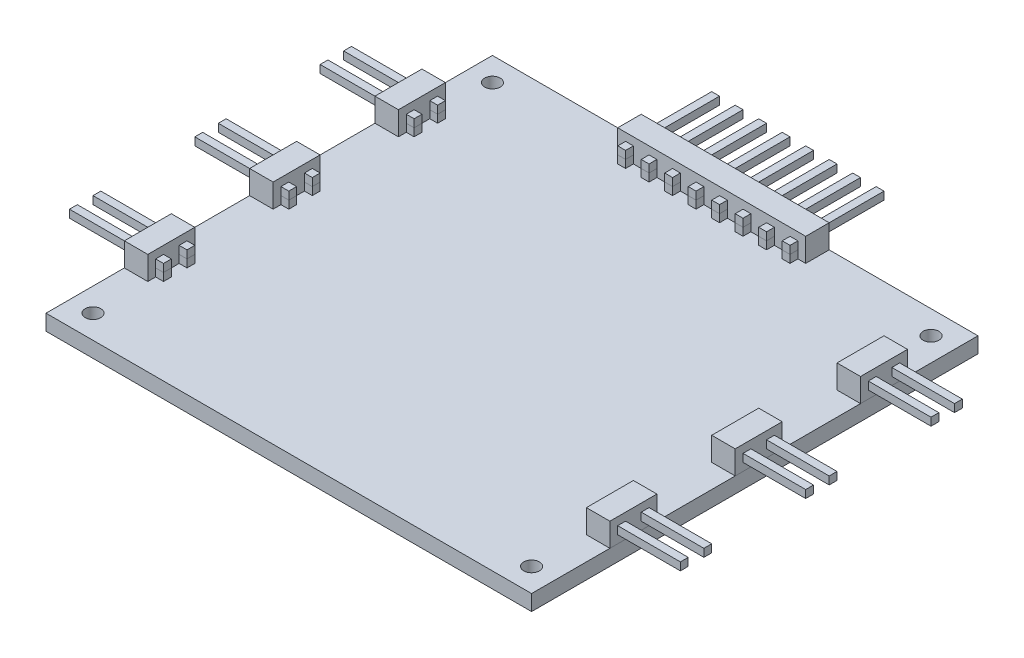
SolidWorks part; units mm, degrees
ref_plane "Front Plane" through (0, 0, 0) normal (0, 0, 1) x (1, 0, 0)
ref_plane "Top Plane" through (0, 0, 0) normal (0, 1, 0) x (1, 0, 0)
ref_plane "Right Plane" through (0, 0, 0) normal (1, 0, 0) x (0, 0, -1)
sketch "Sketch1" plane through (0, 0, 0) normal (0, 1, 0) x (1, 0, 0)
  line L1 (-24.6063, 22.6219) -> (24.6062, 22.6219)
  line L2 (-24.6063, 22.6219) -> (-24.6063, -22.6219)
  line L3 (-24.6063, -22.6219) -> (24.6062, -22.6219)
  line L4 (24.6062, 22.6219) -> (24.6062, -22.6219)
  line L5 (-24.6063, 22.6219) -> (24.6062, -22.6219) construction
  line L6 (-24.6063, -22.6219) -> (24.6062, 22.6219) construction
  point P0 (0, 0)
  dimension "D1" = 49.2125
  dimension "D2" = 45.2437
extrude "Boss-Extrude2" add sketch "Sketch1" along normal blind 1.5875
sketch "Sketch2" plane through (0, 1.5875, 0) normal (0, 1, 0) x (1, 0, 0)
  line L0 (24.6062, -22.6219) -> (24.6062, 22.6219) construction
  line L1 (21.4312, 13.8906) -> (30.9562, 13.8906)
  line L2 (21.4312, 13.8906) -> (21.4312, 14.6844)
  line L3 (21.4312, 14.6844) -> (30.9562, 14.6844)
  line L4 (30.9562, 13.8906) -> (30.9562, 14.6844)
  line L5 (21.4312, 12.3031) -> (30.9562, 12.3031)
  line L6 (21.4312, 12.3031) -> (21.4312, 11.5094)
  line L7 (21.4312, 11.5094) -> (30.9562, 11.5094)
  line L8 (30.9562, 12.3031) -> (30.9562, 11.5094)
  line L9 (24.6062, 22.6219) -> (-24.6063, 22.6219) construction
  line L10 (21.4313, 1.1906) -> (21.4313, 1.9844)
  line L11 (21.4313, 1.1906) -> (30.9563, 1.1906)
  line L12 (30.9563, 1.1906) -> (30.9563, 1.9844)
  line L13 (21.4313, 1.9844) -> (30.9563, 1.9844)
  line L14 (21.4313, -0.3969) -> (21.4313, -1.1906)
  line L15 (21.4313, -0.3969) -> (30.9563, -0.3969)
  line L16 (30.9563, -0.3969) -> (30.9563, -1.1906)
  line L17 (21.4313, -1.1906) -> (30.9563, -1.1906)
  line L18 (21.4313, -11.5094) -> (21.4313, -10.7156)
  line L19 (21.4313, -11.5094) -> (30.9563, -11.5094)
  line L20 (30.9563, -11.5094) -> (30.9563, -10.7156)
  line L21 (21.4313, -10.7156) -> (30.9563, -10.7156)
  line L22 (21.4313, -13.0969) -> (21.4313, -13.8906)
  line L23 (21.4313, -13.0969) -> (30.9563, -13.0969)
  line L24 (30.9563, -13.0969) -> (30.9563, -13.8906)
  line L25 (21.4313, -13.8906) -> (30.9563, -13.8906)
  line L26 (0, 22.6219) -> (0, -22.6219) construction
  line L27 (-24.6063, -22.6219) -> (24.6062, -22.6219) construction
  line L28 (-21.4313, -13.8906) -> (-30.9563, -13.8906)
  line L29 (-30.9563, -13.0969) -> (-30.9563, -13.8906)
  line L30 (-21.4313, -13.0969) -> (-30.9563, -13.0969)
  line L31 (-21.4313, -13.0969) -> (-21.4313, -13.8906)
  line L32 (-21.4313, -10.7156) -> (-30.9563, -10.7156)
  line L33 (-30.9563, -11.5094) -> (-30.9563, -10.7156)
  line L34 (-21.4313, -11.5094) -> (-30.9563, -11.5094)
  line L35 (-21.4313, -11.5094) -> (-21.4313, -10.7156)
  line L36 (-21.4313, -1.1906) -> (-30.9563, -1.1906)
  line L37 (-30.9563, -0.3969) -> (-30.9563, -1.1906)
  line L38 (-21.4313, -0.3969) -> (-30.9563, -0.3969)
  line L39 (-21.4313, -0.3969) -> (-21.4313, -1.1906)
  line L40 (-21.4313, 1.9844) -> (-30.9563, 1.9844)
  line L41 (-30.9563, 1.1906) -> (-30.9563, 1.9844)
  line L42 (-21.4313, 1.1906) -> (-30.9563, 1.1906)
  line L43 (-21.4313, 1.1906) -> (-21.4313, 1.9844)
  line L44 (-30.9563, 12.3031) -> (-30.9563, 11.5094)
  line L45 (-21.4313, 11.5094) -> (-30.9563, 11.5094)
  line L46 (-21.4313, 12.3031) -> (-21.4313, 11.5094)
  line L47 (-21.4313, 12.3031) -> (-30.9563, 12.3031)
  line L48 (-30.9563, 13.8906) -> (-30.9563, 14.6844)
  line L49 (-21.4313, 14.6844) -> (-30.9563, 14.6844)
  line L50 (-21.4313, 13.8906) -> (-21.4313, 14.6844)
  line L51 (-21.4313, 13.8906) -> (-30.9563, 13.8906)
  line L52 (-22.225, -10.7156) -> (-22.225, -11.5094)
  line L53 (-22.225, -13.0969) -> (-22.225, -13.8906)
  line L54 (-22.225, -0.3969) -> (-22.225, -1.1906)
  line L55 (-22.225, 1.9844) -> (-22.225, 1.1906)
  line L56 (-22.225, 12.3031) -> (-22.225, 11.5094)
  line L57 (-22.225, 14.6844) -> (-22.225, 13.8906)
  line L58 (22.225, -13.0969) -> (22.225, -13.8906)
  line L59 (22.225, -10.7156) -> (22.225, -11.5094)
  line L60 (22.225, -0.3969) -> (22.225, -1.1906)
  line L61 (22.225, 1.9844) -> (22.225, 1.1906)
  line L62 (22.225, 12.3031) -> (22.225, 11.5094)
  line L63 (22.225, 14.6844) -> (22.225, 13.8906)
  line M12 (-24.6063, 22.6219) -> (-24.6063, -22.6219)
  dimension "D1" = 0.7937
  dimension "D2" = 1.5875
  dimension "D3" = 3.175
  dimension "D4" = 9.525
  dimension "D5" = 7.9375
  dimension "D7" = 0.7937
  dimension "D6" = 3
extrude "Boss-Extrude4" add sketch "Sketch2" along normal blind 0.7937 separate body contours L49 L57 L51 L50 | L47 L56 L45 L46 | L40 L55 L42 L43 | L38 L54 L36 L39 | L32 L52 L34 L35 | L30 L53 L28 L31 | L60 L15 L14 L17 | L61 L13 L10 L11 | L59 L21 L18 L19 | L58 L23 L22 L25 | L63 L3 L2 L1 | L62 L5 L6 L7 region at (21.8281, 1.5875, -14.2875) region at (21.8281, 1.5875, -11.9063) region at (21.8281, 1.5875, -1.5875) region at (21.8281, 1.5875, 0.7937) region at (21.8281, 1.5875, 11.1125) region at (21.8281, 1.5875, 13.4937) region at (-21.8281, 1.5875, 13.4937) region at (-21.8281, 1.5875, 11.1125) region at (-21.8281, 1.5875, 0.7937) region at (-21.8281, 1.5875, -1.5875) region at (-21.8281, 1.5875, -11.9063) region at (-21.8281, 1.5875, -14.2875)
extrude "Boss-Extrude5" add sketch "Sketch2<3>" along normal blind 0.7937 from offset 0.7937 separate body contours L49 L57 L51 L50 | L57 L49 L51 M12 | L51 L49 L48 M12 | L47 L44 L45 M12 | L56 L47 L45 M12 | L47 L56 L45 L46 | L40 L41 L42 L43 | L38 L37 L36 L39 | L32 L33 L34 L35 | L30 L29 L28 L31 | L19 L20 L21 L18 | L25 L24 L23 L22 | L15 L16 L17 L14 | L13 L12 L11 L10 | L5 L8 L7 L6 | L3 L4 L1 L2 region at (-27.7813, 1.5875, -14.2875) region at (-23.4156, 1.5875, -14.2875) region at (-27.7813, 1.5875, -11.9062) region at (-23.4156, 1.5875, -11.9063) region at (-21.8281, 1.5875, -11.9062) region at (-21.8281, 1.5875, -14.2875)
sketch "Sketch2<3>" plane through (0, 1.5875, 0) normal (0, 1, 0) x (1, 0, 0) same geometry as "Sketch2"
sketch "Sketch3" plane through (0, 1.5875, 0) normal (0, 1, 0) x (1, 0, 0)
  line L0 (-24.6063, 22.6219) -> (-24.6063, -22.6219) construction
  line L1 (-24.6063, 10.7156) -> (-22.225, 10.7156)
  line L2 (-24.6063, 10.7156) -> (-24.6063, 15.4781)
  line L3 (-24.6063, 15.4781) -> (-22.225, 15.4781)
  line L4 (-22.225, 10.7156) -> (-22.225, 15.4781)
  line L5 (-21.4313, 11.5094) -> (-30.9563, 11.5094) construction
  line L6 (-21.4313, 14.6844) -> (-30.9563, 14.6844) construction
  line L7 (-24.6062, -1.9844) -> (-24.6062, 2.7781)
  line L8 (-24.6062, -1.9844) -> (-22.225, -1.9844)
  line L9 (-22.225, -1.9844) -> (-22.225, 2.7781)
  line L10 (-24.6062, 2.7781) -> (-22.225, 2.7781)
  line L11 (-24.6062, -14.6844) -> (-24.6062, -9.9219)
  line L12 (-24.6062, -14.6844) -> (-22.225, -14.6844)
  line L13 (-22.225, -14.6844) -> (-22.225, -9.9219)
  line L14 (-24.6062, -9.9219) -> (-22.225, -9.9219)
  line L15 (0, 22.6219) -> (0, -22.6219) construction
  line L16 (24.6062, 22.6219) -> (-24.6063, 22.6219) construction
  line L17 (-24.6063, -22.6219) -> (24.6062, -22.6219) construction
  line L18 (24.6062, -9.9219) -> (22.225, -9.9219)
  line L19 (22.225, -14.6844) -> (22.225, -9.9219)
  line L20 (24.6062, -14.6844) -> (22.225, -14.6844)
  line L21 (24.6062, -14.6844) -> (24.6062, -9.9219)
  line L22 (24.6062, 2.7781) -> (22.225, 2.7781)
  line L23 (22.225, -1.9844) -> (22.225, 2.7781)
  line L24 (24.6062, -1.9844) -> (22.225, -1.9844)
  line L25 (24.6062, -1.9844) -> (24.6062, 2.7781)
  line L26 (22.225, 10.7156) -> (22.225, 15.4781)
  line L27 (24.6062, 15.4781) -> (22.225, 15.4781)
  line L28 (24.6062, 10.7156) -> (24.6062, 15.4781)
  line L29 (24.6062, 10.7156) -> (22.225, 10.7156)
  dimension "D1" = 0.7937
  dimension "D2" = 0.7937
  dimension "D3" = 2.3813
  dimension "D4" = 3
extrude "Boss-Extrude6" add sketch "Sketch3" along normal blind 2.3813 separate body
sketch "Sketch4" plane through (0, 1.5875, 0) normal (0, 1, 0) x (1, 0, 0)
  line L0 (0, 22.6219) -> (0, 0) construction
  line L1 (24.6062, 22.6219) -> (-24.6063, 22.6219) construction
  line L2 (8.7312, 19.4469) -> (8.7312, 28.9719)
  line L3 (-0.7938, 19.4469) -> (-1.5875, 19.4469)
  line L4 (-0.7938, 19.4469) -> (-0.7938, 28.9719)
  line L5 (-0.7938, 28.9719) -> (-1.5875, 28.9719)
  line L6 (-1.5875, 19.4469) -> (-1.5875, 28.9719)
  line L7 (-3.175, 19.4469) -> (-3.9688, 19.4469)
  line L8 (-3.175, 19.4469) -> (-3.175, 28.9719)
  line L9 (-3.175, 28.9719) -> (-3.9688, 28.9719)
  line L10 (-3.9688, 19.4469) -> (-3.9688, 28.9719)
  line L11 (-5.5563, 19.4469) -> (-6.35, 19.4469)
  line L12 (-5.5563, 19.4469) -> (-5.5563, 28.9719)
  line L13 (-5.5563, 28.9719) -> (-6.35, 28.9719)
  line L14 (-6.35, 19.4469) -> (-6.35, 28.9719)
  line L15 (-7.9375, 19.4469) -> (-8.7313, 19.4469)
  line L16 (-7.9375, 19.4469) -> (-7.9375, 28.9719)
  line L17 (-7.9375, 28.9719) -> (-8.7313, 28.9719)
  line L18 (-8.7313, 19.4469) -> (-8.7313, 28.9719)
  line L19 (7.9375, 28.9719) -> (8.7312, 28.9719)
  line L20 (7.9375, 19.4469) -> (7.9375, 28.9719)
  line L21 (7.9375, 19.4469) -> (8.7312, 19.4469)
  line L22 (6.35, 19.4469) -> (6.35, 28.9719)
  line L23 (5.5562, 28.9719) -> (6.35, 28.9719)
  line L24 (5.5562, 19.4469) -> (5.5562, 28.9719)
  line L25 (5.5562, 19.4469) -> (6.35, 19.4469)
  line L26 (3.9687, 19.4469) -> (3.9687, 28.9719)
  line L27 (3.175, 28.9719) -> (3.9687, 28.9719)
  line L28 (3.175, 19.4469) -> (3.175, 28.9719)
  line L29 (3.175, 19.4469) -> (3.9687, 19.4469)
  line L30 (1.5875, 19.4469) -> (1.5875, 28.9719)
  line L31 (0.7937, 28.9719) -> (1.5875, 28.9719)
  line L32 (0.7937, 19.4469) -> (0.7937, 28.9719)
  line L33 (0.7937, 19.4469) -> (1.5875, 19.4469)
  line L34 (-8.7313, 20.2406) -> (-7.9375, 20.2406)
  line L35 (-6.35, 20.2406) -> (-5.5563, 20.2406)
  line L36 (-3.9688, 20.2406) -> (-3.175, 20.2406)
  line L37 (-1.5875, 20.2406) -> (-0.7938, 20.2406)
  line L38 (0.7938, 20.2406) -> (1.5875, 20.2406)
  line L39 (3.175, 20.2406) -> (3.9688, 20.2406)
  line L40 (5.5563, 20.2406) -> (6.35, 20.2406)
  line L41 (7.9375, 20.2406) -> (8.7313, 20.2406)
  dimension "D1" = 1.5875
  dimension "D2" = 1.5875
  dimension "D3" = 1.5875
  dimension "D4" = 0.7937
  dimension "D5" = 1.5875
  dimension "D6" = 3.175
  dimension "D7" = 6.35
  dimension "D8" = 0.7937
extrude "Boss-Extrude7" add sketch "Sketch4" along normal blind 0.7937 separate body contours L34 L18 L15 L16 | L35 L14 L11 L12 | L36 L10 L7 L8 | L37 L6 L3 L4 | L38 L32 L33 L30 | L39 L28 L29 L26 | L40 L24 L25 L22 | L41 L20 L21 L2 region at (8.3344, 1.5875, -19.8438) region at (-1.1906, 1.5875, -19.8438) region at (-3.5719, 1.5875, -19.8438) region at (-5.9531, 1.5875, -19.8438) region at (-8.3344, 1.5875, -19.8438) region at (5.9531, 1.5875, -19.8438) region at (3.5719, 1.5875, -19.8438) region at (1.1906, 1.5875, -19.8438)
extrude "Boss-Extrude8" add sketch "Sketch4<3>" along normal blind 0.7937 from offset 0.7937 separate body contours L16 L17 L18 L15 | L12 L13 L14 L11 | L8 L9 L10 L7 | L4 L5 L6 L3 | L30 L31 L32 L33 | L26 L27 L28 L29 | L22 L23 L24 L25 | L2 L19 L20 L21
sketch "Sketch4<3>" plane through (0, 1.5875, 0) normal (0, 1, 0) x (1, 0, 0) same geometry as "Sketch4"
sketch "Sketch5" plane through (0, 1.5875, 0) normal (0, 1, 0) x (1, 0, 0)
  line L0 (24.6062, 22.6219) -> (-24.6063, 22.6219) construction
  line L1 (-9.525, 22.6219) -> (9.525, 22.6219)
  line L2 (-9.525, 22.6219) -> (-9.525, 20.2406)
  line L3 (-9.525, 20.2406) -> (9.525, 20.2406)
  line L4 (9.525, 22.6219) -> (9.525, 20.2406)
  line L5 (-8.7313, 19.4469) -> (-8.7313, 28.9719) construction
  line L6 (8.7312, 19.4469) -> (8.7312, 28.9719) construction
  dimension "D1" = 2.3813
  dimension "D2" = 0.7937
  dimension "D3" = 0.7937
extrude "Boss-Extrude9" add sketch "Sketch5" along normal blind 2.3813 separate body
sketch "Sketch12" plane through (0, 1.5875, 0) normal (0, 1, 0) x (1, 0, 0)
  line L0 (24.6062, 22.6219) -> (-24.6063, 22.6219) construction
  line L1 (-24.6063, 22.6219) -> (-24.6063, -22.6219) construction
  line L2 (-22.225, 20.2406) -> (-22.225, -20.2406) construction
  line L3 (-22.225, -20.2406) -> (22.225, -20.2406) construction
  line L4 (22.225, -20.2406) -> (22.225, 20.2406) construction
  line L5 (22.225, 20.2406) -> (-22.225, 20.2406) construction
  line L6 (24.6062, -22.6219) -> (24.6062, 22.6219) construction
  line L7 (-24.6063, -22.6219) -> (24.6062, -22.6219) construction
  circle A0 centre (-22.225, 20.2406) radius 0.7937
  circle A1 centre (-22.225, -20.2406) radius 0.7937
  circle A2 centre (22.225, -20.2406) radius 0.7937
  circle A3 centre (22.225, 20.2406) radius 0.7937
  dimension "D1" = 1.5875
  dimension "D2" = 2.3813
  dimension "D3" = 2.3813
  dimension "D4" = 2.3813
  dimension "D5" = 2.3813
extrude "Cut-Extrude1" cut sketch "Sketch12" against normal through all
